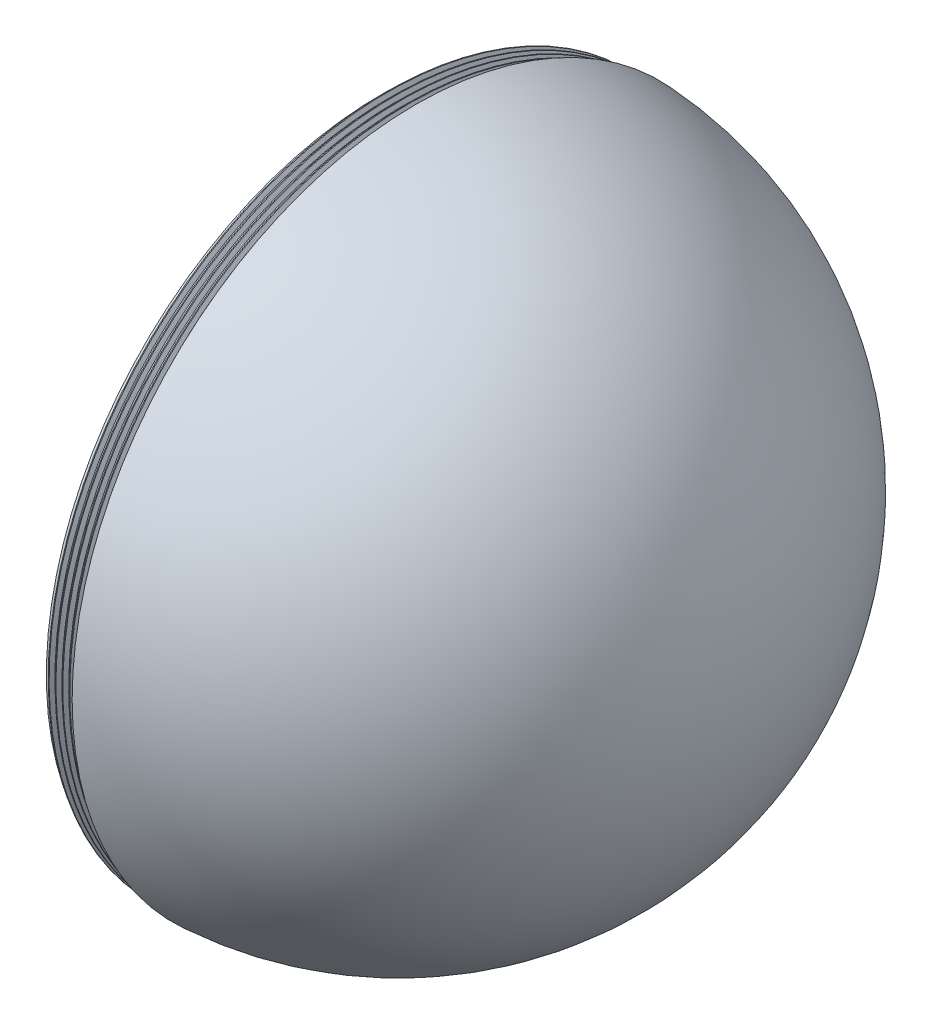
SolidWorks part; units mm, degrees
ref_plane "Front Plane" through (0, 0, 0) normal (0, 0, 1) x (1, 0, 0)
ref_plane "Top Plane" through (0, 0, 0) normal (0, 1, 0) x (1, 0, 0)
ref_plane "Right Plane" through (0, 0, 0) normal (1, 0, 0) x (0, 0, -1)
sketch "Sketch1" plane through (0, 0, 0) normal (0, 0, 1) x (1, 0, 0)
  line L0 (0, 97.5) -> (0, 0) construction
  line L1 (5, 99.8749) -> (5, 0) construction
  line L2 (-5, 99.8749) -> (-5, 0) construction
  line L3 (-5, 0) -> (100, 0) construction
  line L4 (-5, 97.3717) -> (-5, 94.8683)
  line L7 (95, 0) -> (100, 0)
  line L8 (-5, 97.3717) -> (5, 97.3717)
  line L9 (5, 97.3717) -> (5, 99.8749)
  arc A0 (100, 0) -> (5, 99.8749) centre (0, 0) ccw
  arc A3 (95, 0) -> (-5, 94.8683) centre (0, 0) ccw
  arc A4 (97.5, 0) -> (-5, 97.3717) centre (0, 0) ccw construction
  dimension "D1" = 100
  dimension "D2" = 97.5
  dimension "D3" = 95
  dimension "D4" = 5
  dimension "D5" = 5
revolve "Revolve3" add sketch "Sketch1" angle 360 about L3
thread "Thread1" pitch 2 method extrude profile "Thread Profile2" start angle 0, offset 0, length 0, pitch 2, diameter 194.7434
ref_plane "Plane2" through (-5, 0, -97.3717) normal (0, -1, 0) x (0, 0, -1)
sketch "Thread Profile2" plane through (-5, 0, -97.3717) normal (0, -1, 0) x (0, 0, -1)
  line L0 (0, 0) -> (0, 2) construction
  line L1 (0, 0) -> (1.0825, 0.625)
  line L2 (1.0825, 0.625) -> (1.0825, 0.875)
  line L3 (1.0825, 0.875) -> (0, 1.5)
  line L4 (1.0825, 0.75) -> (0, 0.75) construction
  line L11 (0, 0) -> (0, 1.5)
  point P2 (0, 0)
  dimension "Pitch" = 2
  dimension "Profile_Angle" = 60
  dimension "Profile_Land" = 0.25
  dimension "Profile_Height" = 1.0825
